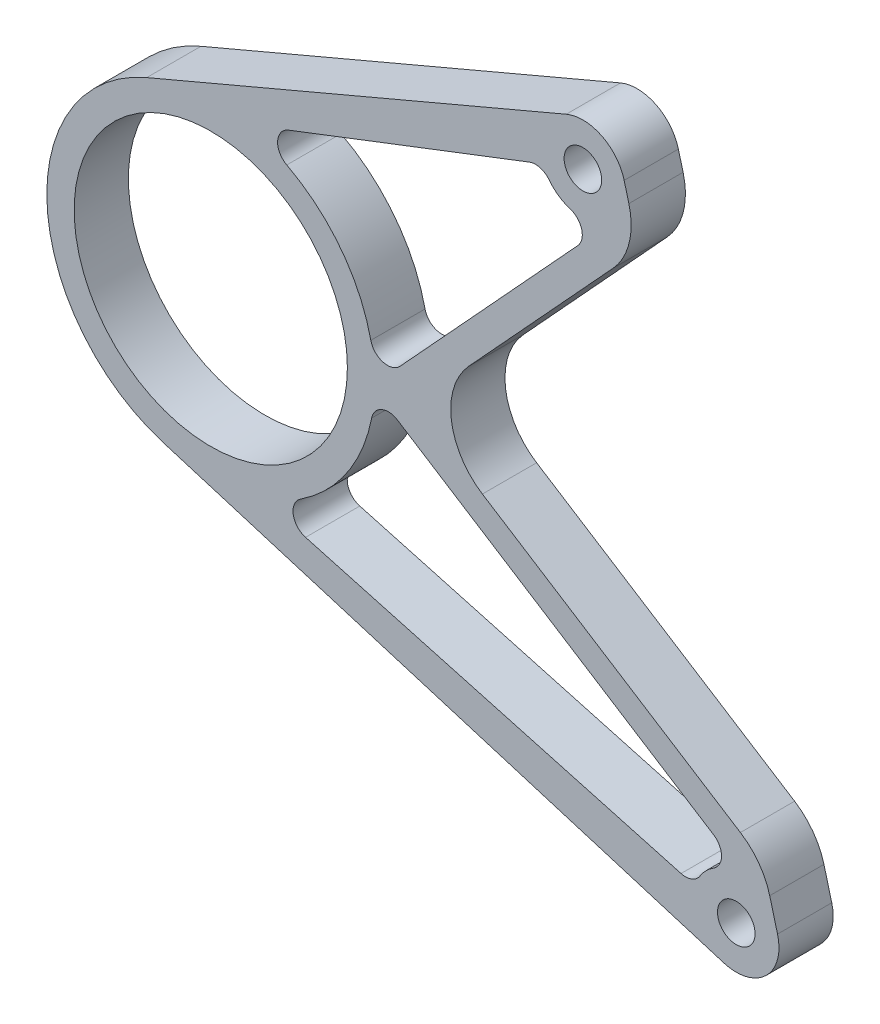
SolidWorks part; units mm, degrees
material "6061-T6 (SS)"
ref_plane "Front Plane" through (0, 0, 0) normal (0, 0, 1) x (1, 0, 0)
ref_plane "Top Plane" through (0, 0, 0) normal (0, 1, 0) x (1, 0, 0)
ref_plane "Right Plane" through (0, 0, 0) normal (1, 0, 0) x (0, 0, -1)
sketch "Sketch2" plane through (0, 0, 0) normal (0, 0, 1) x (1, 0, 0)
  line L0 (0, 0) -> (47.1306, -195.9686) construction
  line L1 (47.1306, -195.9686) -> (-302.8687, -196.6579) construction
  line L2 (-302.8687, -196.6579) -> (-257.3584, -0.3067) construction
  line L3 (-257.3584, -0.3067) -> (0, 0) construction
  line L4 (12.1535, 2.9229) -> (59.2841, -193.0457) construction
  line L5 (-12.1535, -2.9229) -> (34.9771, -198.8916) construction
  line L6 (0.0149, -12.5) -> (-257.3435, -12.8067) construction
  line L7 (-257.3733, 12.1933) -> (-0.0149, 12.5) construction
  line L8 (-269.5356, 2.5158) -> (-315.0459, -193.8355) construction
  line L9 (-290.6915, -199.4803) -> (-245.1812, -3.1291) construction
  line L10 (-302.8441, -209.1579) -> (47.1552, -208.4686) construction
  line L11 (-302.8933, -184.1579) -> (47.106, -183.4687) construction
  line L14 (-0.0149, 12.5) -> (-257.5094, 12.1932) construction
  line L15 (-287.5987, -186.1366) -> (-245.1812, -3.1291) construction
  circle A0 centre (0, 0) radius 12.5 construction
  circle A1 centre (47.1306, -195.9686) radius 12.5 construction
  circle A2 centre (-302.8687, -196.6579) radius 12.5 construction
  circle A3 centre (-257.3584, -0.3067) radius 12.5 construction
  circle A4 centre (47.1306, -195.9686) radius 12.5 construction
  arc A5 (-302.8933, -184.1579) -> (-302.8441, -209.1579) centre (-302.8687, -196.6579) ccw construction
sketch "Sketch4" plane through (0, 0, 0) normal (0, 0, 1) x (1, 0, 0)
  line L0 (-149.2073, -56.7645) -> (-5.3459, 11.2992) construction
  line L1 (-143.8125, -145.7054) -> (43.1897, -207.8311) construction
  line L2 (-128.6792, -100.1534) -> (47.1306, -195.9686) construction
  line L3 (12.1535, 2.9229) -> (59.2841, -193.0457) construction
  line L4 (-128.6792, -100.1534) -> (0, 0) construction
  line L5 (-142.6339, -146.0802) -> (21.5449, -195.9652)
  line L6 (37.2581, -180.7887) -> (-7.6495, -12.1388)
  line L7 (-24.6116, -3.8484) -> (-147.4299, -55.9673)
  line L8 (-257.3584, -0.3067) -> (0, 0) construction
  arc A0 (-149.2073, -56.7645) -> (-143.8125, -145.7054) centre (-128.6792, -100.1534) ccw construction
  arc A1 (-5.3459, 11.2992) -> (12.1535, 2.9229) centre (0, 0) cw construction
  arc A2 (43.1897, -207.8311) -> (59.2841, -193.0457) centre (47.1306, -195.9686) ccw construction
  circle A3 centre (47.1306, -195.9686) radius 12.5 construction
  circle A4 centre (0, 0) radius 12.5 construction
  circle A5 centre (-128.6792, -100.1534) radius 40 construction
  circle A6 centre (-128.6792, -100.1534) radius 121 construction
  circle A7 centre (-128.6792, -100.1534) radius 40
  arc A8 (-147.4299, -55.9673) -> (-142.6339, -146.0802) centre (-128.6792, -100.1534) ccw
  arc A9 (21.5449, -195.9652) -> (37.2581, -180.7887) centre (25.179, -184.0051) ccw
  arc A10 (-7.6495, -12.1388) -> (-24.6116, -3.8484) centre (-19.7286, -15.3552) ccw
  circle A11 centre (25.179, -184.0051) radius 5.5
  circle A12 centre (-19.7286, -15.3552) radius 5.5
  point P29 (-128.6792, -0.1533)
  dimension "D1" = 80
  dimension "D2" = 8
  dimension "D3" = 242
  dimension "D4" = 11
  dimension "D5" = 7
  dimension "D6" = 100
extrude "Boss-Extrude1" add sketch "Sketch4" along normal blind 15.875
sketch "Sketch5" plane through (0, 0, 15.875) normal (0, 0, 1) x (1, 0, 0)
  line L0 (-143.0483, -62.8234) -> (-19.7286, -15.3552)
  line L1 (-10.5248, -23.8132) -> (-80.6792, -100.1534)
  line L2 (-139.2976, -138.7183) -> (25.179, -184.0051)
  line L3 (-80.7084, -101.8286) -> (31.8884, -173.4584)
  line L4 (-128.6792, -100.1534) -> (-80.6792, -100.1534) construction
  line L5 (-80.7084, -101.8286) -> (-128.6792, -100.1534) construction
  circle A0 centre (-128.6792, -100.1534) radius 48
  arc A1 (-147.4299, -55.9673) -> (-142.6339, -146.0802) centre (-128.6792, -100.1534) ccw construction
  circle A2 centre (-19.7286, -15.3552) radius 12.5
  circle A3 centre (25.179, -184.0051) radius 12.5
  arc A4 (-7.6495, -12.1388) -> (-24.6116, -3.8484) centre (-19.7286, -15.3552) ccw construction
  circle A5 centre (-128.6792, -100.1534) radius 40 construction
  arc A6 (21.5449, -195.9652) -> (37.2581, -180.7887) centre (25.179, -184.0051) ccw construction
  dimension "D1" = 2
extrude "Cut-Extrude2" cut sketch "Sketch5" against normal through all contours A2 L0 A0 L1 | A3 L3 A0 L2 region at (-64.7358, -53.4499, 15.875) region at (-46.2329, -145.9947, 15.875)
fillet "Fillet1" radius 5 8 edges at (31.8884, -173.4584, 7.9375) (13.1274, -180.6869, 7.9375) (-80.7084, -101.8286, 7.9375) (-113.7166, -145.7617, 7.9375) (-80.6792, -100.1534, 7.9375) (-118.2864, -53.292, 7.9375) (-10.5248, -23.8132, 7.9375) (-31.3943, -19.8455, 7.9375)
sketch "Sketch6" plane through (0, 0, 15.875) normal (0, 0, 1) x (1, 0, 0)
  line L0 (-69.3062, -99.6006) -> (-3.4443, -27.9315)
  line L1 (37.2581, -180.7887) -> (-7.6495, -12.1388) construction
  line L2 (-69.3062, -99.6006) -> (32.9636, -164.6608)
  line L3 (32.9636, -164.6608) -> (-3.4443, -27.9315)
  line L4 (-21.2235, -35.4553) -> (-73.2525, -92.0719) construction
  line L5 (-73.981, -106.1083) -> (18.5477, -164.9716) construction
  line L6 (-44.0562, -72.1242) -> (-49.9466, -66.711) construction
  line L7 (-26.7207, -126.6919) -> (-31.0147, -133.4418) construction
  dimension "D1" = 8
extrude "Cut-Extrude3" cut sketch "Sketch6" against normal through all
fillet "Fillet2" radius 20 3 edges at (32.9636, -164.6608, 7.9375) (-69.3062, -99.6006, 7.9375) (-3.4443, -27.9315, 7.9375)
sketch "Sketch8" plane through (0, 0, 0) normal (0, 0, 1) x (1, 0, 0)
  line L0 (-257.3584, -0.3067) -> (-346.2284, -83.1582) construction
  line L1 (-346.2284, -83.1582) -> (-302.8687, -196.6579) construction
  circle A0 centre (-346.2284, -83.1582) radius 104 construction
  circle A1 centre (-257.3584, -0.3067) radius 12.5 construction
  circle A2 centre (-302.8687, -196.6579) radius 12.5 construction
  point P2 (-270.1586, -12.24)
  point P3 (-266.5014, -8.8305)
  point P5 (-309.1139, -180.3102)
  point P10 (-307.3296, -184.981)
  dimension "D1" = 208
  dimension "D2" = 5
  dimension "D3" = 5
